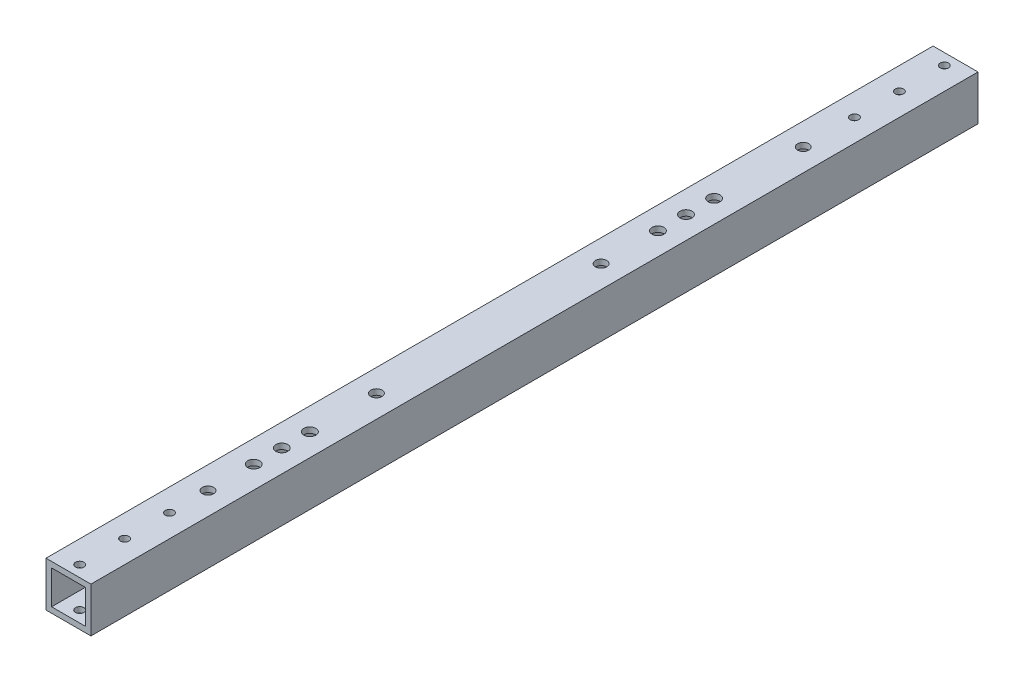
SolidWorks part; units mm, degrees
material "6061-T6 (SS)"
ref_plane "Front Plane" through (0, 0, 0) normal (0, 0, 1) x (1, 0, 0)
ref_plane "Top Plane" through (0, 0, 0) normal (0, 1, 0) x (1, 0, 0)
ref_plane "Right Plane" through (0, 0, 0) normal (1, 0, 0) x (0, 0, -1)
sketch "Sketch1" plane through (0, 0, 0) normal (0, 0, 1) x (1, 0, 0)
  line L1 (-12.7, -12.7) -> (12.7, -12.7)
  line L2 (-12.7, -12.7) -> (-12.7, 12.7)
  line L3 (-12.7, 12.7) -> (12.7, 12.7)
  line L4 (12.7, -12.7) -> (12.7, 12.7)
  line L5 (-12.7, -12.7) -> (12.7, 12.7) construction
  line L6 (-12.7, 12.7) -> (12.7, -12.7) construction
  point P0 (0, 0)
  dimension "D1" = 25.4
  dimension "D2" = 25.4
extrude "Extrude-Thin1" add sketch "Sketch1" along normal blind 501.65 thin thin type one direction reverse wall 3.175
hole_wizard "3/16 (0.1875) Diameter Hole1" positions "3DSketch1" profile "Sketch3" hole size "3/16" standard "ANSI Inch" end condition through all
sketch3d "3DSketch1"
  line L1 (12.7, 12.7, 0) -> (-12.7, 12.7, 0) construction
  line L6 (0, 12.7, 501.65) -> (0, 12.7, 0) construction
  line L7 (12.7, 12.7, 501.65) -> (-12.7, 12.7, 501.65) construction
  point P57 (0, 12.7, 6.35)
  point P59 (0, 12.7, 31.75)
  point P61 (0, 12.7, 57.15)
  point P63 (0, 12.7, 469.9)
  point P65 (0, 12.7, 444.5)
  point P67 (0, 12.7, 495.3)
  dimension "D1" = 25.4
  dimension "D2" = 25.4
  dimension "D3" = 6.35
  dimension "D4" = 25.4
  dimension "D5" = 25.4
  dimension "D6" = 6.35
sketch "Sketch3" plane through (0, 12.7, 495.3) normal (1, 0, 0) x (0, 0, 1)
  line L0 (0, 0) -> (0, 25.4)
  line L1 (0, 25.4) -> (2.3812, 25.4)
  line L2 (2.3812, 25.4) -> (2.3812, 0)
  line L5 (2.3812, 0) -> (0, 0)
  line L11 (0, -6.35) -> (0, 107.95) construction
  dimension "Thru Hole Dia." = 4.7625
  dimension "Thru Hole Depth" = 25.4
hole_wizard "1/4 (0.25) Diameter Hole1" positions "Sketch6" profile "Sketch7" hole size "1/4" standard "ANSI Inch"
sketch "Sketch6" plane through (0, 12.7, 0) normal (0, 1, 0) x (1, 0, 0)
  point P0 (0, -200.4645)
  point P15 (0, -422.731)
  point P23 (0, -327.481)
  point P26 (0, -86.1545)
sketch "Sketch7" plane through (0, 12.7, 200.4645) normal (1, 0, 0) x (0, 0, 1)
  line L0 (0, 0) -> (0, 27.3077)
  line L1 (0, 27.3077) -> (3.175, 25.4)
  line L2 (3.175, 25.4) -> (3.175, 0)
  line L5 (3.175, 0) -> (0, 0)
  line L10 (0, 27.3077) -> (-3.175, 25.4) construction
  line L11 (0, -6.35) -> (0, 107.95) construction
  dimension "Hole Dia." = 6.35
  dimension "Hole Depth" = 25.4
  dimension "Drill Angle" = 118
hole_wizard "1/4 Clearance Hole1" positions "Sketch17" profile "Sketch18" hole size "1/4" standard "ANSI Inch"
sketch "Sketch17" plane through (-381, 12.7, 250.825) normal (0, 1, 0) x (1, 0, 0)
  point P0 (381, 82.55)
  point P3 (381, 98.425)
  point P6 (381, 114.3)
  point P9 (381, -146.05)
  point P12 (381, -130.175)
  point P15 (381, -114.3)
  point P18 (-381, -146.05)
  point P21 (-381, -130.175)
  point P24 (-381, -114.3)
  point P27 (-381, 82.55)
  point P30 (-381, 98.425)
  point P33 (-381, 114.3)
sketch "Sketch18" plane through (0, 12.7, 168.275) normal (1, 0, 0) x (0, 0, 1)
  line L0 (0, 0) -> (0, 40.1298)
  line L1 (0, 40.1298) -> (3.3782, 38.1)
  line L2 (3.3782, 38.1) -> (3.3782, 0)
  line L3 (3.3782, 0) -> (0, 0)
  line L4 (0, 40.1298) -> (-3.3782, 38.1) construction
  line L5 (0, -6.35) -> (0, 107.95) construction
  dimension "Hole Dia." = 6.7564
  dimension "Hole Depth" = 38.1
  dimension "Drill Angle" = 118
